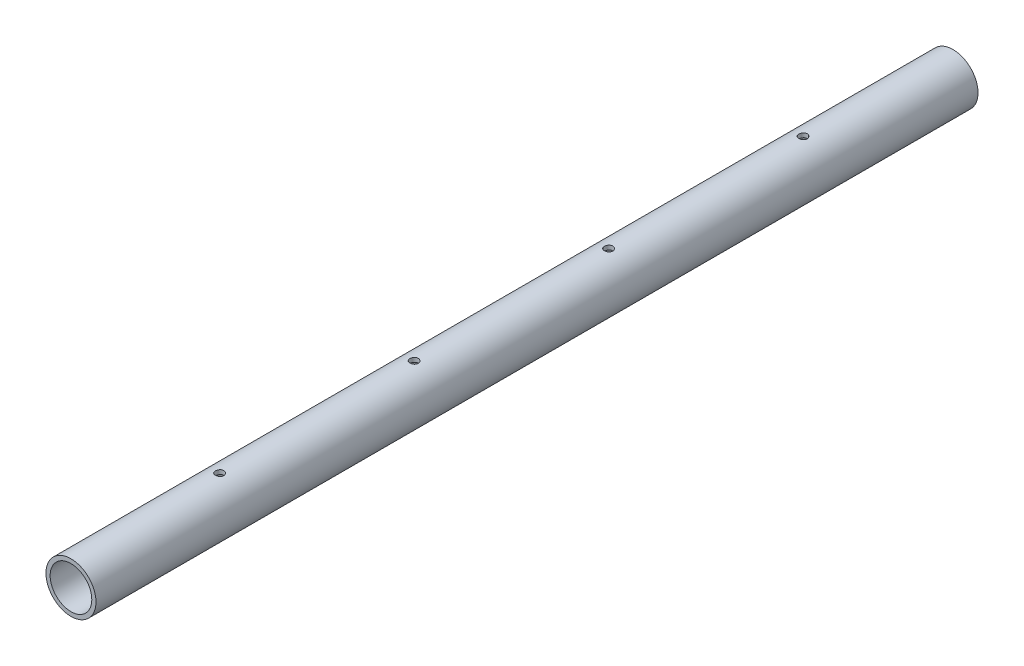
SolidWorks part; units mm, degrees
ref_plane "Plan de face" through (0, 0, 0) normal (0, 0, 1) x (1, 0, 0)
ref_plane "Plan de dessus" through (0, 0, 0) normal (0, 1, 0) x (1, 0, 0)
ref_plane "Plan de droite" through (0, 0, 0) normal (1, 0, 0) x (0, 0, -1)
sketch "Esquisse1" plane through (0, 0, 0) normal (0, 0, 1) x (1, 0, 0)
  circle A0 centre (0, 0) radius 15
extrude "Extru.-Mince1" add sketch "Esquisse1" along normal blind 635 thin thin type one direction wall 3
sketch "Esquisse2" plane through (0, 0, 0) normal (0, 1, 0) x (1, 0, 0)
  line L0 (15, 0) -> (-15, 0) construction
  circle A0 centre (0, -108) radius 3
  dimension "D1" = 108
extrude "Enlèv. mat.-Extru.1" cut sketch "Esquisse2" against normal blind 30 and the other way blind 30
pattern_linear "Répétition linéaire1" count 4 spacing 140 along (0, 0, 1) of "Enlèv. mat.-Extru.1"
